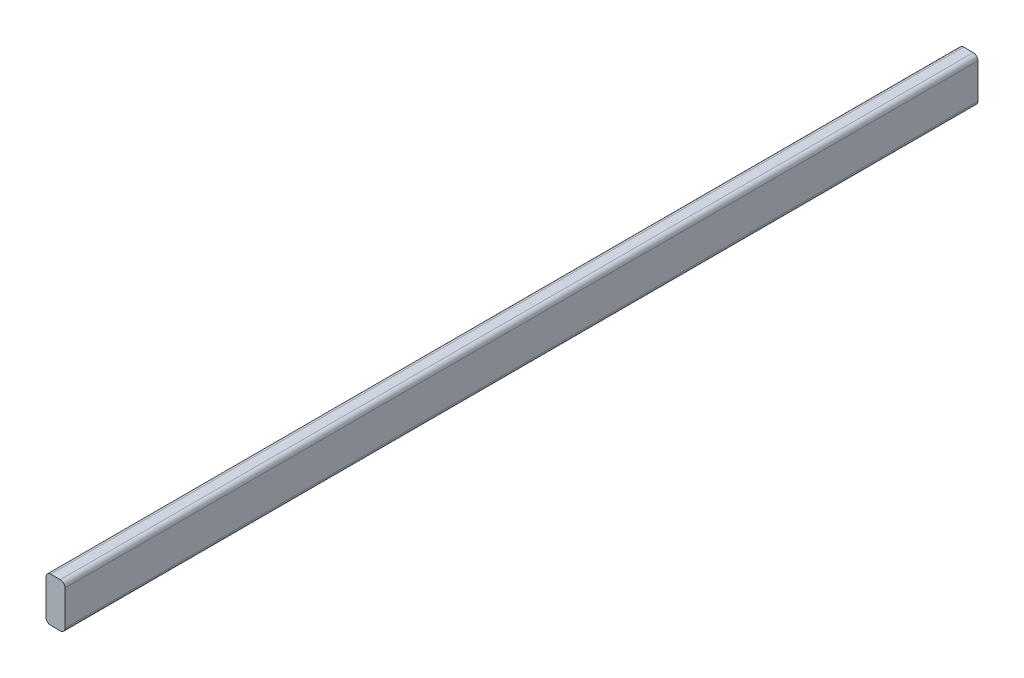
SolidWorks part; units mm, degrees
ref_plane "Front Plane" through (0, 0, 0) normal (0, 0, 1) x (1, 0, 0)
ref_plane "Top Plane" through (0, 0, 0) normal (0, 1, 0) x (1, 0, 0)
ref_plane "Right Plane" through (0, 0, 0) normal (1, 0, 0) x (0, 0, -1)
sketch "Sketch1" plane through (0, 0, 0) normal (0, 0, 1) x (1, 0, 0)
  line L0 (-9.525, 22.225) -> (-9.525, -22.225) construction
  line L1 (-9.525, 22.225) -> (9.525, 22.225) construction
  line L2 (-9.525, 0) -> (0, 0) construction
  line L3 (0, 0) -> (0, 22.225) construction
  dimension "Thickness" = 19.05
  dimension "Width" = 44.45
ref_plane "Plane1" through (-9.525, 22.225, 0) normal (0, -1, 0) x (-1, 0, 0)
sketch "Sketch2" plane through (-9.525, 22.225, 0) normal (0, 1, 0) x (1, 0, 0)
  line L0 (9.525, -457.2) -> (9.525, 457.2) construction
  point P2 (9.525, -390.525)
  point P3 (9.525, 390.525)
  dimension "Length" = 914.4
  dimension "D1" = 66.675
  dimension "D2" = 66.675
sketch "Sketch3" plane through (0, 0, 0) normal (0, 0, 1) x (1, 0, 0)
  line L1 (-9.525, -22.225) -> (9.525, -22.225)
  line L2 (-9.525, -22.225) -> (-9.525, 22.225)
  line L3 (-9.525, 22.225) -> (9.525, 22.225)
  line L4 (9.525, -22.225) -> (9.525, 22.225)
  line L5 (0, 22.225) -> (0, -22.225) construction
  line L6 (-9.525, 0) -> (9.525, 0) construction
  line L7 (-9.525, 0) -> (0, 0) construction
extrude "Boss-Extrude1" add sketch "Sketch3" along normal up to vertex (457.2 mm away) and the other way up to vertex (457.2 mm away) up to point (0, 22.225, 457.2) other way up to point (0, 22.225, -457.2)
fillet "Fillet1" radius 4.7625 4 edges at (9.525, -22.225, 0) (-9.525, -22.225, 0) (9.525, 22.225, 0) (-9.525, 22.225, 0)
sketch "Sketch4" plane through (9.525, 0, 0) normal (1, 0, 0) x (0, 0, -1)
  line L0 (457.2, -17.4625) -> (457.2, 17.4625) construction
  line L1 (-9.525, 22.225) -> (-457.2, 22.225)
  line L2 (-9.525, 22.225) -> (-9.525, -22.225)
  line L3 (-9.525, -22.225) -> (-457.2, -22.225)
  line L4 (-457.2, 22.225) -> (-457.2, -22.225)
  line L5 (9.525, 22.225) -> (457.2, 22.225)
  line L6 (9.525, 22.225) -> (9.525, -22.225)
  line L7 (9.525, -22.225) -> (457.2, -22.225)
  line L8 (457.2, 22.225) -> (457.2, -22.225)
  line L9 (-457.2, 22.225) -> (457.2, 22.225) construction
  line L10 (457.2, -22.225) -> (-457.2, -22.225) construction
  line L11 (-457.2, -17.4625) -> (-457.2, 17.4625) construction
  line L12 (-9.525, 0) -> (9.525, 0)
  point P20 (0, 0)
  dimension "D1" = 19.05
equation "\"D1@Sketch2\"=\"Width@Sketch1\"*1.5"
equation "\"D2@Sketch2\"=\"D1@Sketch2\""
equation "\"D1@Fillet1\"=\"Thickness@Sketch1\"/4"
